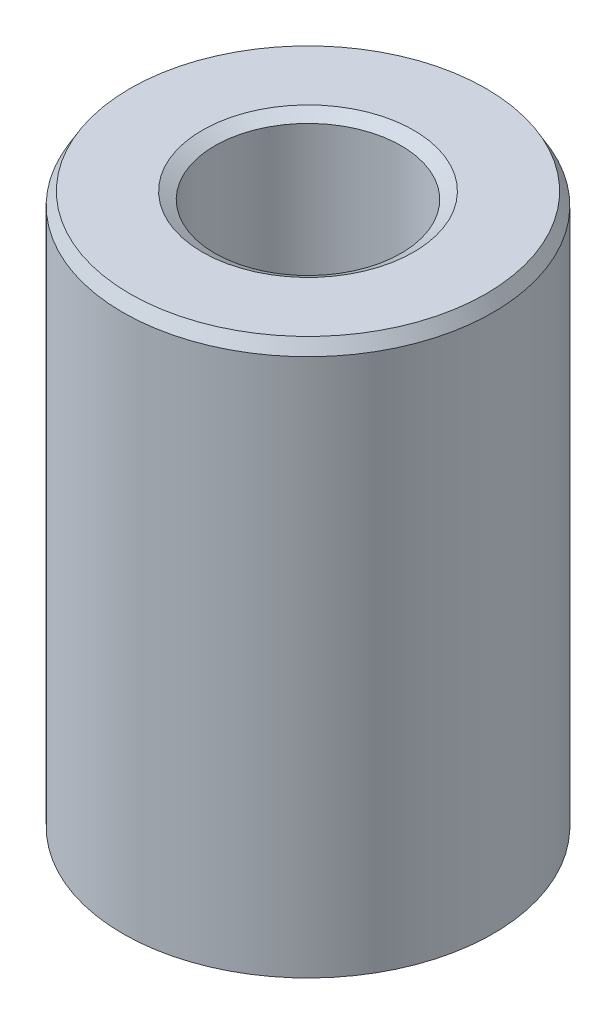
SolidWorks part; units mm, degrees
ref_plane "Front Plane" through (0, 0, 0) normal (0, 0, 1) x (1, 0, 0)
ref_plane "Top Plane" through (0, 0, 0) normal (0, 1, 0) x (1, 0, 0)
ref_plane "Right Plane" through (0, 0, 0) normal (1, 0, 0) x (0, 0, -1)
sketch "Sketch1" plane through (0, 0, 0) normal (0, 1, 0) x (1, 0, 0)
  circle A0 centre (0, 0) radius 55
  dimension "SLEEVE_OD" = 110
extrude "Boss-Extrude1" add sketch "Sketch1" along normal blind 165.6813
sketch "Sketch2" plane through (0, 0, 0) normal (0, 1, 0) x (1, 0, 0)
  circle A0 centre (0, 0) radius 27.6856
  dimension "BORE_D" = 55.3713
extrude "Cut-Extrude1" cut sketch "Sketch2" along normal through all
chamfer "Chamfer1" distance 3.7053 angle 30 4 edges at (0, 165.6813, 27.6856) (0, 0, 27.6856) (0, 0, 55) (0, 165.6813, 55) first distance on face at (0, 165.6813, 27.6856) first distance on face at (0, 0, 27.6856) first distance on face at (0, 165.6813, 55)
